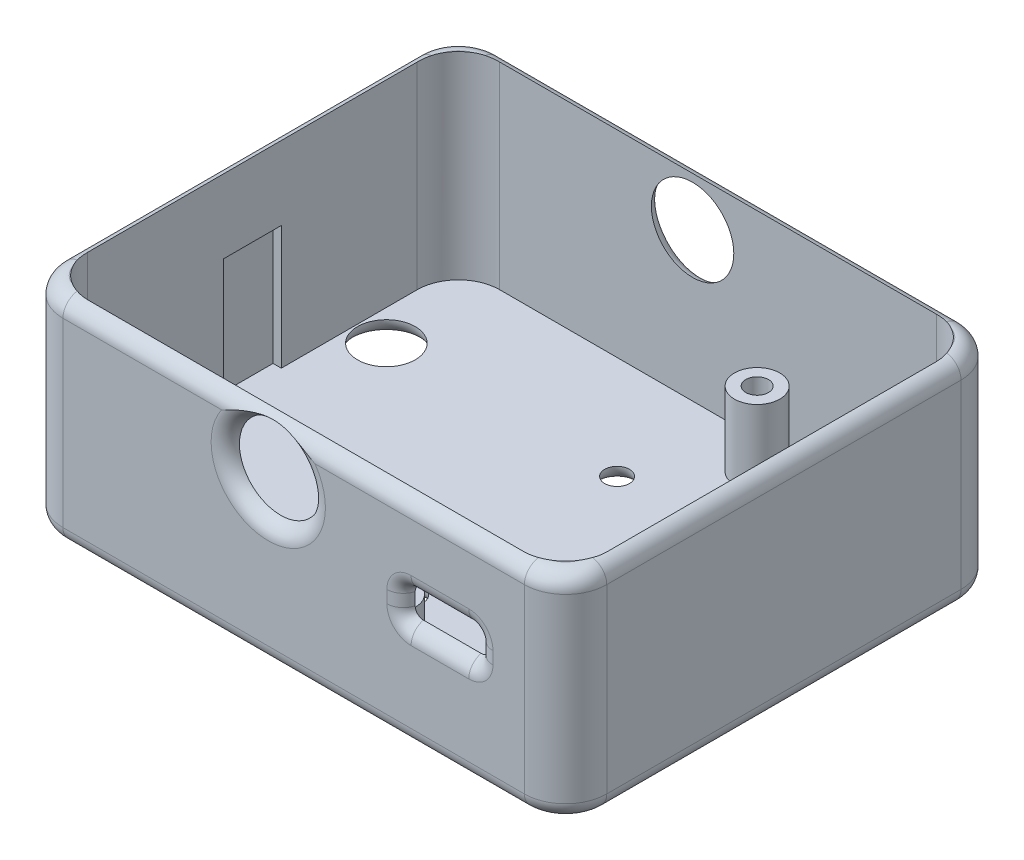
SolidWorks part; units mm, degrees
ref_plane "Front Plane" through (0, 0, 0) normal (0, 0, 1) x (1, 0, 0)
ref_plane "Top Plane" through (0, 0, 0) normal (0, 1, 0) x (1, 0, 0)
ref_plane "Right Plane" through (0, 0, 0) normal (1, 0, 0) x (0, 0, -1)
sketch "Sketch1" plane through (0, 0, 0) normal (0, 1, 0) x (1, 0, 0)
  line L1 (-29.9185, 15.0305) -> (26.0815, 15.0305)
  line L2 (-34.9185, 10.0305) -> (-34.9185, -32.9695)
  line L3 (-29.9185, -37.9695) -> (26.0815, -37.9695)
  line L4 (31.0815, 10.0305) -> (31.0815, -32.9695)
  arc A0 (-34.9185, -32.9695) -> (-29.9185, -37.9695) centre (-29.9185, -32.9695) ccw
  arc A1 (26.0815, -37.9695) -> (31.0815, -32.9695) centre (26.0815, -32.9695) ccw
  arc A2 (31.0815, 10.0305) -> (26.0815, 15.0305) centre (26.0815, 10.0305) ccw
  arc A3 (-29.9185, 15.0305) -> (-34.9185, 10.0305) centre (-29.9185, 10.0305) ccw
  point P8 (31.0815, -37.9695)
  point P11 (31.0815, 15.0305)
  point P14 (-34.9185, 15.0305)
  dimension "D3" = 5
  dimension "D1" = 66
  dimension "D2" = 53
extrude "Boss-Extrude1" add sketch "Sketch1" along normal blind 26
sketch "Sketch2" plane through (0, 26, 0) normal (0, 1, 0) x (1, 0, 0)
  line L0 (26.0815, 15.0305) -> (-29.9185, 15.0305) construction
  line L1 (-28.4185, 13.5305) -> (24.5815, 13.5305)
  line L2 (-33.4185, 8.5305) -> (-33.4185, -31.4695)
  line L3 (-28.4185, -36.4695) -> (24.5815, -36.4695)
  line L4 (29.5815, 8.5305) -> (29.5815, -31.4695)
  line L5 (31.0815, -32.9695) -> (31.0815, 10.0305) construction
  line L6 (-29.9185, -37.9695) -> (26.0815, -37.9695) construction
  line L7 (-34.9185, 10.0305) -> (-34.9185, -32.9695) construction
  arc A0 (-33.4185, -31.4695) -> (-28.4185, -36.4695) centre (-28.4185, -31.4695) ccw
  arc A1 (24.5815, -36.4695) -> (29.5815, -31.4695) centre (24.5815, -31.4695) ccw
  arc A2 (29.5815, 8.5305) -> (24.5815, 13.5305) centre (24.5815, 8.5305) ccw
  arc A3 (-28.4185, 13.5305) -> (-33.4185, 8.5305) centre (-28.4185, 8.5305) ccw
  dimension "D1" = 5
  dimension "D2" = 1.5
  dimension "D3" = 1.5
  dimension "D4" = 1.5
  dimension "D5" = 1.5
extrude "Cut-Extrude1" cut sketch "Sketch2" against normal blind 24
sketch "Sketch3" plane through (0, 2, 0) normal (0, 1, 0) x (1, 0, 0)
  line L0 (31.0815, -32.9695) -> (31.0815, 10.0305) construction
  line L2 (-29.9185, -37.9695) -> (26.0815, -37.9695) construction
  circle A0 centre (27.3315, 10.0298) radius 2.75
  circle A1 centre (27.0815, -33.9695) radius 2.75
  circle A2 centre (6.0815, -33.9695) radius 2.75
  circle A3 centre (6.3315, 10.0298) radius 2.75
  dimension "D5" = 5.5
  dimension "D6" = 5.5
  dimension "D7" = 5.5
  dimension "D8" = 5.5
  dimension "D9" = 4
  dimension "D10" = 4
  dimension "D1" = 44
  dimension "D2" = 44
  dimension "D3" = 21
  dimension "D4" = 21
extrude "Boss-Extrude2" add sketch "Sketch3" along normal blind 9
sketch "Sketch4" plane through (0, 11, 0) normal (0, 1, 0) x (1, 0, 0)
  circle A0 centre (6.3315, 10.0298) radius 1.375
  circle A1 centre (27.3315, 10.0298) radius 1.375
  circle A2 centre (6.0815, -33.9695) radius 1.375
  circle A3 centre (27.0815, -33.9695) radius 1.375
  circle A4 centre (6.3315, 10.0298) radius 2.75 construction
  arc A5 (27.2202, 12.7776) -> (29.5815, 8.4487) centre (27.3315, 10.0298) ccw construction
  dimension "D1" = 2.75
  dimension "D2" = 2.75
  dimension "D3" = 2.75
  dimension "D4" = 2.75
  dimension "D5" = 0
  dimension "D6" = 0
extrude "Cut-Extrude2" cut sketch "Sketch4" against normal blind 9 and the other way blind 9
sketch "Sketch5" plane through (0, 11, 0) normal (0, 1, 0) x (1, 0, 0)
  circle A0 centre (27.0815, -33.9695) radius 2
  circle A1 centre (27.3315, 10.0298) radius 2
  dimension "D1" = 4
  dimension "D2" = 4
extrude "Cut-Extrude3" cut sketch "Sketch5" along normal blind 9
sketch "Sketch6" plane through (0, 0, 36.4695) normal (0, 0, -1) x (-1, 0, 0)
  line L0 (-7.2271, 11) -> (-4.9358, 11) construction
  line L1 (-12.3315, 12.65) -> (-19.3315, 12.65)
  line L2 (-11.3315, 13.65) -> (-11.3315, 15.15)
  line L3 (-12.3315, 16.15) -> (-19.3315, 16.15)
  line L4 (-20.3315, 13.65) -> (-20.3315, 15.15)
  arc A0 (-11.3315, 15.15) -> (-12.3315, 16.15) centre (-12.3315, 15.15) ccw
  arc A1 (-19.3315, 16.15) -> (-20.3315, 15.15) centre (-19.3315, 15.15) ccw
  arc A2 (-20.3315, 13.65) -> (-19.3315, 12.65) centre (-19.3315, 13.65) ccw
  arc A3 (-12.3315, 12.65) -> (-11.3315, 13.65) centre (-12.3315, 13.65) ccw
  point P6 (-11.3315, 16.15)
  point P11 (-20.3315, 12.65)
  point P14 (-11.3315, 12.65)
  point P19 (-6.0815, 11)
  dimension "D3" = 1
  dimension "D1" = 9
  dimension "D2" = 3.5
  dimension "D4" = 1.65
  dimension "D5" = 5.25
extrude "Cut-Extrude4" cut sketch "Sketch6" against normal blind 9
sketch "Sketch7" plane through (0, 2, 0) normal (0, 1, 0) x (1, 0, 0)
  line L0 (-28.4185, -36.4695) -> (4.9358, -36.4695) construction
  line L1 (24.5815, 13.5305) -> (-28.4185, 13.5305) construction
  circle A0 centre (-1.6685, 1.0305) radius 1.5
  circle A2 centre (6.3315, 10.0298) radius 2.75 construction
  circle A3 centre (-1.6685, -23.9695) radius 1.5
  circle A5 centre (-29.6685, -23.9695) radius 1.5
  circle A6 centre (-29.6685, 1.0305) radius 3.5
  dimension "D2" = 7
  dimension "D3" = 3
  dimension "D7" = 3
  dimension "D5" = 3
  dimension "D8" = 28
  dimension "D4" = 8
  dimension "D6" = 12.5
  dimension "D9" = 12.5
  dimension "D10" = 25
  dimension "D11" = 28
  dimension "D12" = 25
extrude "Cut-Extrude5" cut sketch "Sketch7" against normal blind 9
sketch "Sketch9" plane through (0, 0, 37.9695) normal (0, 0, 1) x (1, 0, 0)
  line L0 (-29.9185, 0) -> (26.0815, 0) construction
  circle A0 centre (-5, 20) radius 5
  point P5 (0, 20)
  dimension "D2" = 10
  dimension "D1" = 20
  dimension "D3" = 5
extrude "Cut-Extrude6" cut sketch "Sketch9" against normal blind 100
fillet "Fillet2" radius 2 28 edges at (29.617, 26, -13.5661) (29.617, 26, 36.505) (-33.4541, 26, 36.505) (-33.4541, 26, -13.5661) (-1.9185, 26, 37.9695) (11.6244, 12.9429, 37.9695) (15.8315, 12.65, 37.9695) (20.0386, 12.9429, 37.9695) (20.3315, 14.4, 37.9695) (20.0386, 15.8571, 37.9695) (15.8315, 16.15, 37.9695) (11.6244, 15.8571, 37.9695) (11.3315, 14.4, 37.9695) (0, 20, 37.9695) (-1.9185, 0, 37.9695) (29.617, 0, 36.505) (31.0815, 0, 11.4695) (29.617, 0, -13.5661) (-33.4541, 0, -13.5661) (-34.9185, 0, 11.4695) (-33.4541, 0, 36.505) (-1.6685, 0, 25.4695) (-29.6685, 0, 25.4695) (-1.6685, 0, 0.4695) (-1.9185, 26, -15.0305) (-1.9185, 0, -15.0305) (0, 20, -15.0305) (-29.6685, 0, 2.4695)
sketch "Sketch10" plane through (0, 2, 0) normal (0, 1, 0) x (1, 0, 0)
  line L0 (-33.4185, 8.5305) -> (-33.4185, -31.4695) construction
  line L1 (-33.4185, -7.9695) -> (-34.4185, -7.9695)
  line L2 (-33.4185, -7.9695) -> (-33.4185, -14.9695)
  line L3 (-33.4185, -14.9695) -> (-34.4185, -14.9695)
  line L4 (-34.4185, -7.9695) -> (-34.4185, -14.9695)
  dimension "D1" = 1
  dimension "D2" = 7
  dimension "D3" = 16.5
  dimension "D4" = 16.5
extrude "Cut-Extrude7" cut sketch "Sketch10" along normal blind 15
